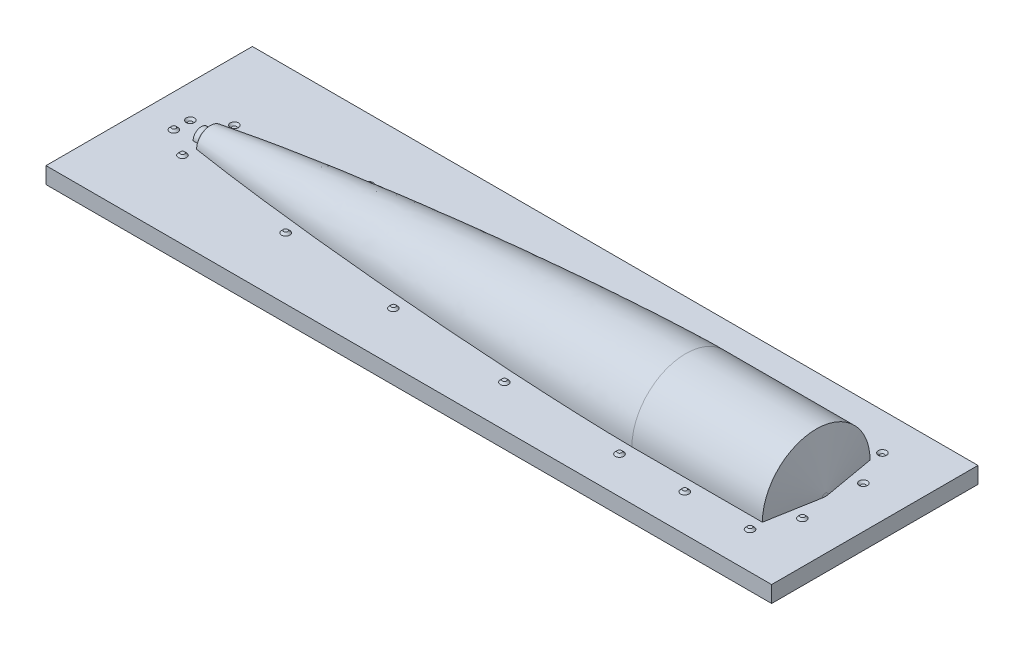
SolidWorks part; units mm, degrees
ref_plane "Front" through (0, 0, 0) normal (0, 0, 1) x (1, 0, 0)
ref_plane "Top" through (0, 0, 0) normal (0, 1, 0) x (1, 0, 0)
ref_plane "Right" through (0, 0, 0) normal (1, 0, 0) x (0, 0, -1)
other "von Karman body"
sketch "Sketch1" plane through (0, 0, 0) normal (0, 1, 0) x (1, 0, 0)
  line L0 (838.2, 83.82) -> (1041.4, 83.82)
  line L1 (1041.4, 83.82) -> (1055.402, 4.4107)
  line L2 (1055.7879, 0) -> (79.7661, 0)
  line L3 (96.6803, 12.7) -> (83.9803, 12.7)
  line L4 (96.6803, 12.7) -> (98.2259, 21.4654)
  line L5 (83.9803, 12.7) -> (80.7329, 4.8601)
  line L6 (0, 0) -> (1055.7879, 0) construction
  line L7 (83.9803, 12.7) -> (82.9291, 18.9624) construction
  line L8 (79.7661, 0) -> (79.7661, 6.839) construction
  circle A0 centre (3.2859, 0) radius 1.5875 construction
  arc A1 (80.7329, 4.8601) -> (79.7661, 0) centre (92.4661, 0) ccw
  arc A2 (1055.402, 4.4107) -> (1055.7879, 0) centre (1030.3879, 0) cw
  spline S0 degree 4 poles (0.0014, -0.0139) (0.0044, -0.0057) (0.0116, 0.0101) (0.0314, 0.0387) (0.0663, 0.0774) (0.1098, 0.1198) (0.1756, 0.1763) (0.2578, 0.2402) (0.43, 0.3617) (0.6491, 0.4956) (0.898, 0.6345) (1.1966, 0.7887) (1.4641, 0.9197) (1.9053, 1.1256) (2.6908, 1.4661) (4.1174, 2.0276) (6.8315, 2.9752) (11.8195, 4.4991) (21.1817, 6.9737) (37.5192, 10.6769) (65.2764, 16.0894) (103.3878, 22.4749) (149.5828, 29.2977) (200.9556, 36.0951) (252.4018, 42.3062) (303.9044, 48.03) (355.4522, 53.3298) (407.0382, 58.2429) (458.6575, 62.7928) (510.3066, 66.9901) (561.9831, 70.8361) (613.6852, 74.3214) (665.4118, 77.4242) (710.6933, 79.7692) (749.5207, 81.4699) (780.8317, 82.597) (801.9098, 83.2137) (819.2261, 83.6007) (830.0679, 83.7618) (835.4892, 83.8132) (838.2, 83.82) knots 0 0 0 0 0 0.000041 0.000082 0.000164 0.000247 0.000329 0.000493 0.000658 0.001245 0.001545 0.001844 0.002251 0.002657 0.003853 0.005902 0.009516 0.016281 0.028569 0.051794 0.088907 0.150314 0.211721 0.273128 0.334535 0.395942 0.457348 0.518755 0.580162 0.641569 0.702976 0.764383 0.825789 0.887196 0.9179 0.948603 0.974302 0.987151 1 1 1 1 1 construction
  spline S1 degree 4 poles (98.2259, 21.4654) (104.6543, 22.4927) (123.8878, 25.4864) (155.972, 30.1431) (200.9556, 36.0951) (252.4018, 42.3062) (303.9044, 48.03) (355.4522, 53.3298) (407.0382, 58.2429) (458.6575, 62.7928) (510.3066, 66.9901) (561.9831, 70.8361) (613.6852, 74.3214) (665.4118, 77.4242) (710.6933, 79.7692) (749.5207, 81.4699) (780.8317, 82.597) (801.9098, 83.2137) (819.2261, 83.6007) (830.0679, 83.7618) (835.4892, 83.8132) (838.2, 83.82) knots 0.119456 0.119456 0.119456 0.119456 0.119456 0.150314 0.211721 0.273128 0.334535 0.395942 0.457348 0.518755 0.580162 0.641569 0.702976 0.764383 0.825789 0.887196 0.9179 0.948603 0.974302 0.987151 1 1 1 1 1
  spline S2 degree 4 poles (0, 0) (0.003, 0.0082) (0.0102, 0.024) (0.03, 0.0526) (0.0649, 0.0913) (0.1084, 0.1337) (0.1742, 0.1902) (0.2565, 0.254) (0.4287, 0.3755) (0.6477, 0.5094) (0.8967, 0.6483) (1.1954, 0.8025) (1.4629, 0.9334) (1.9041, 1.1393) (2.6896, 1.4796) (4.1163, 2.0409) (6.8305, 2.9882) (11.8188, 4.5114) (21.1813, 6.9846) (37.5193, 10.6856) (65.2772, 16.0943) (103.3896, 22.4744) (149.5855, 29.2908) (200.9592, 36.0811) (252.4063, 42.285) (303.9097, 48.0016) (355.4582, 53.2943) (407.0449, 58.2003) (458.6648, 62.7429) (510.3146, 66.9331) (561.9916, 70.772) (613.6942, 74.2501) (665.4211, 77.3457) (710.703, 79.6843) (749.5307, 81.3797) (780.8418, 82.5024) (801.92, 83.1162) (819.2363, 83.5008) (830.0782, 83.6603) (835.4995, 83.711) (838.2103, 83.7174) knots 0 0 0 0 0 0.000041 0.000082 0.000164 0.000247 0.000329 0.000493 0.000658 0.001245 0.001545 0.001844 0.002251 0.002657 0.003853 0.005902 0.009516 0.016281 0.028569 0.051794 0.088907 0.150314 0.211721 0.273128 0.334535 0.395942 0.457348 0.518755 0.580162 0.641569 0.702976 0.764383 0.825789 0.887196 0.9179 0.948603 0.974302 0.987151 1 1 1 1 1 construction
  spline S3 degree 4 poles (0, 0) (0.003, 0.0082) (0.0102, 0.024) (0.03, 0.0526) (0.0649, 0.0913) (0.1084, 0.1337) (0.1742, 0.1902) (0.2565, 0.254) (0.4287, 0.3755) (0.6477, 0.5094) (0.8967, 0.6483) (1.1954, 0.8025) (1.4629, 0.9334) (1.9041, 1.1393) (2.6896, 1.4796) (4.1163, 2.0409) (6.8305, 2.9882) (11.8188, 4.5114) (21.1813, 6.9846) (37.5193, 10.6856) (58.8862, 14.849) (77.7757, 18.1421) (91.8621, 20.4493) (98.2259, 21.4654) knots 0 0 0 0 0 0.000041 0.000082 0.000164 0.000247 0.000329 0.000493 0.000658 0.001245 0.001545 0.001844 0.002251 0.002657 0.003853 0.005902 0.009516 0.016281 0.028569 0.051794 0.088907 0.119454 0.119454 0.119454 0.119454 0.119454 construction
  point P5 (0, 0)
  dimension "D6" = 3.175
  dimension "D9" = 25.4
  dimension "D10" = 12.7
  dimension "D1" = 12.7
  dimension "D2" = 100
  dimension "D3" = 203.2
  dimension "D4" = 6.35
  dimension "D5" = 838.2
  dimension "D7" = 67.5
  dimension "D8" = 80
  dimension "D11" = 83.82
  dimension "D12" = 12.7
revolve "main body" add sketch "Sketch1" angle 180 about L2 other way angle 180 reverse direction yes
scale "Scale1" scale about centroid uniform scaling yes scale factor 0.991965
sketch "Sketch2" plane through (0, 0.2528, 0) normal (0, -1, 0) x (1, 0, 0)
  line L0 (1052.9291, 0) -> (1129.1291, 0) construction
  line L1 (1129.1291, -159.3465) -> (8.5497, -159.3465)
  line L2 (1129.1291, -159.3465) -> (1129.1291, 159.3465)
  line L3 (1129.1291, 159.3465) -> (8.5497, 159.3465)
  line L4 (8.5497, -159.3465) -> (8.5497, 159.3465)
  line L5 (1038.6568, -83.1465) -> (837.0895, -83.1465) construction
  arc A0 (1052.5463, -4.3752) -> (1052.5463, 4.3752) centre (1027.7332, 0) ccw construction
  arc A1 (85.7087, 4.821) -> (85.7087, -4.821) centre (97.3477, 0) ccw construction
  point P12 (0, 0)
  point P13 (1102.6879, 159.3465)
  point P17 (84.7497, 0)
  dimension "D2" = 76.2
  dimension "D1" = 76.2
  dimension "D3" = 76.2
extrude "Boss-Extrude1" add sketch "Sketch2" along normal blind 25.4
fillet "Fillet1" radius 6.35 1 edges at (101.5279, 12.8508, 0)
sketch "Sketch3" plane through (0, 0.2528, 0) normal (0, 1, 0) x (1, 0, 0)
  line L0 (84.7497, 0) -> (8.5497, 0) construction
  line L3 (8.5497, -159.3465) -> (8.5497, 159.3465) construction
  line L4 (100.0549, -40.1042) -> (103.0611, -21.2929) construction
  line L5 (285.5844, -45.2156) -> (283.4895, -64.1501) construction
  line L6 (467.6376, -81.9245) -> (469.2236, -62.9406) construction
  line L7 (652.1769, -95.0272) -> (653.2764, -76.0089) construction
  line L8 (837.0419, -102.1964) -> (837.0895, -83.1465) construction
  line L9 (1038.6568, -83.1465) -> (837.0895, -83.1465) construction
  line L10 (1038.6568, -102.1965) -> (1038.6568, -83.1465) construction
  line L11 (1052.9291, 0) -> (1129.1291, 0) construction
  line L12 (1129.1291, 159.3465) -> (1129.1291, -159.3465) construction
  line L13 (1064.3622, -47.0689) -> (1045.6016, -43.7609) construction
  line L14 (1052.5463, -4.3752) -> (1038.6568, -83.1465) construction
  line L15 (100.0549, -40.1042) -> (283.4895, -64.1501) construction
  line L16 (283.4895, -64.1501) -> (467.6376, -81.9245) construction
  line L17 (467.6376, -81.9245) -> (652.1769, -95.0272) construction
  line L18 (652.1769, -95.0272) -> (837.0419, -102.1964) construction
  line L19 (937.8732, -102.1965) -> (937.8732, -83.1465) construction
  circle A0 centre (1038.6568, -102.1965) radius 6.35
  circle A1 centre (837.0419, -102.1964) radius 6.35
  circle A2 centre (100.0549, -40.1042) radius 6.35
  circle A3 centre (467.6376, -81.9245) radius 6.35
  circle A4 centre (283.4895, -64.1501) radius 6.35
  circle A5 centre (652.1769, -95.0272) radius 6.35
  circle A6 centre (59.3497, -12.7) radius 6.35
  circle A7 centre (1064.3622, -47.0689) radius 6.35
  arc A9 (85.7087, 4.821) -> (85.7087, -4.821) centre (97.3477, 0) ccw construction
  arc A10 (1052.5463, -4.3752) -> (1052.5463, 4.3752) centre (1027.7332, 0) ccw construction
  circle A11 centre (937.8732, -102.1965) radius 6.35
  spline S0 degree 4 poles (837.0895, -83.1465) (834.4006, -83.1398) (829.0228, -83.0888) (818.2681, -82.929) (801.091, -82.5451) (780.1822, -81.9334) (749.1228, -80.8153) (710.6073, -79.1282) (665.6897, -76.8021) (614.3787, -73.7243) (563.0921, -70.267) (511.8308, -66.4518) (460.5967, -62.2882) (409.3922, -57.7749) (358.2206, -52.9013) (307.0871, -47.644) (255.9982, -41.9663) (204.9654, -35.8051) (160.3432, -29.9009) (128.5168, -25.2816) (109.4379, -22.312) (103.0611, -21.2929) knots 0.119456 0.119456 0.119456 0.119456 0.119456 0.132305 0.145154 0.170853 0.201556 0.23226 0.293667 0.355073 0.41648 0.477887 0.539294 0.600701 0.662108 0.723514 0.784921 0.846328 0.907735 0.969142 1 1 1 1 1 construction
  point P48 (937.8732, -83.1465)
  dimension "D1" = 12.7
  dimension "D2" = 12.7
  dimension "D3" = 25.4
  dimension "D4" = 19.05
extrude "Boss-Extrude2" add sketch "Sketch3" along normal blind 3.175 draft 45
sketch "Sketch4" plane through (0, 0.2528, 0) normal (0, 1, 0) x (1, 0, 0)
  line L0 (8.5497, 0) -> (1129.1291, 0) construction
  line L1 (8.5497, -159.3465) -> (8.5497, 159.3465) construction
  line L2 (1129.1291, 159.3465) -> (1129.1291, -159.3465) construction
  circle A0 centre (1038.6568, 102.1965) radius 6.35
  circle A1 centre (1064.3622, -47.0689) radius 6.35
  circle A2 centre (1064.3622, -47.0689) radius 6.35 construction
  circle A3 centre (59.3497, -12.7) radius 6.35
  circle A4 centre (59.3497, -12.7) radius 6.35 construction
  circle A5 centre (652.1769, -95.0272) radius 6.35
  circle A6 centre (652.1769, -95.0272) radius 6.35 construction
  circle A7 centre (283.4895, -64.1501) radius 6.35
  circle A8 centre (283.4895, -64.1501) radius 6.35 construction
  circle A9 centre (467.6376, -81.9245) radius 6.35
  circle A10 centre (467.6376, -81.9245) radius 6.35 construction
  circle A11 centre (100.0549, -40.1042) radius 6.35
  circle A12 centre (100.0549, -40.1042) radius 6.35 construction
  circle A13 centre (837.0419, -102.1964) radius 6.35
  circle A14 centre (837.0419, -102.1964) radius 6.35 construction
  circle A15 centre (1038.6568, -102.1965) radius 6.35
  circle A16 centre (1038.6568, -102.1965) radius 6.35 construction
  circle A17 centre (837.0419, 102.1964) radius 6.35
  circle A18 centre (100.0549, 40.1042) radius 6.35
  circle A19 centre (467.6376, 81.9245) radius 6.35
  circle A20 centre (283.4895, 64.1501) radius 6.35
  circle A21 centre (652.1769, 95.0272) radius 6.35
  circle A22 centre (59.3497, 12.7) radius 6.35
  circle A23 centre (1064.3622, 47.0689) radius 6.35
  circle A24 centre (937.8732, 102.1965) radius 6.35
  circle A25 centre (937.8732, -102.1965) radius 6.35
  circle A26 centre (937.8732, -102.1965) radius 6.35 construction
  dimension "D1" = 0
  dimension "D2" = 0
  dimension "D3" = 0
  dimension "D4" = 0
  dimension "D5" = 0
  dimension "D6" = 0
  dimension "D7" = 0
  dimension "D8" = 0
  dimension "D9" = 0
extrude "Cut-Extrude1" cut sketch "Sketch4" against normal blind 3.175 draft 45
